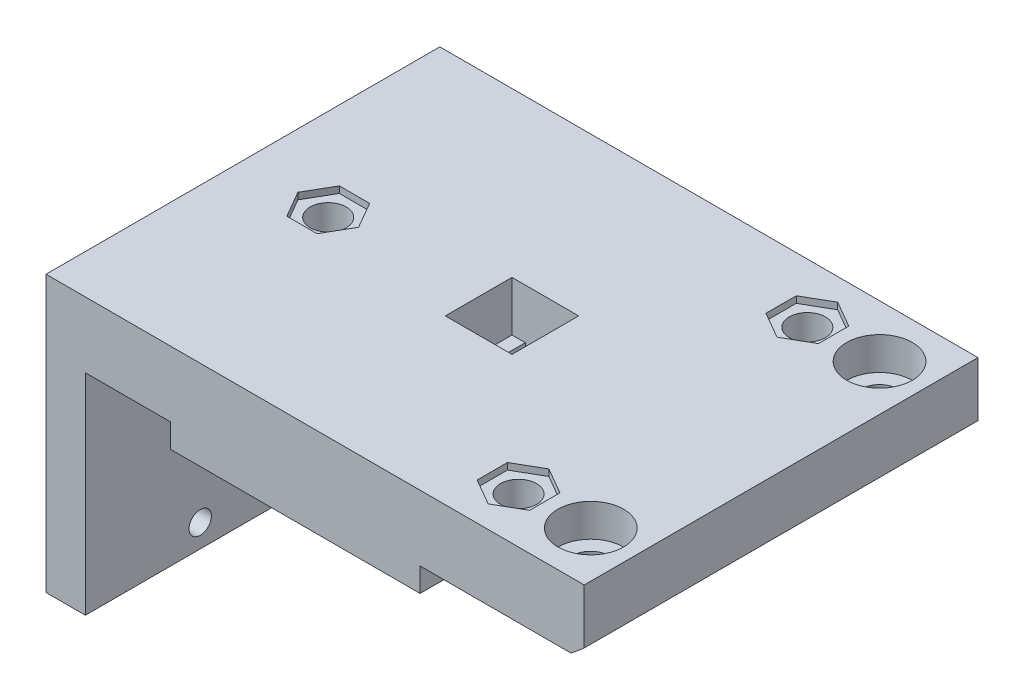
SolidWorks part; units mm, degrees
ref_plane "Front Plane" through (0, 0, 0) normal (0, 0, 1) x (1, 0, 0)
ref_plane "Top Plane" through (0, 0, 0) normal (0, 1, 0) x (1, 0, 0)
ref_plane "Right Plane" through (0, 0, 0) normal (1, 0, 0) x (0, 0, -1)
sketch "Sketch1" plane through (0, 0, 0) normal (0, 1, 0) x (1, 0, 0)
  line L1 (0, 0) -> (82, 0)
  line L2 (0, 0) -> (0, 60)
  line L3 (0, 60) -> (82, 60)
  line L4 (82, 0) -> (82, 60)
  dimension "D1" = 82
  dimension "D2" = 60
extrude "Boss-Extrude1" add sketch "Sketch1" along normal blind 10
sketch "Sketch2" plane through (0, 0, 0) normal (0, -1, 0) x (1, 0, 0)
  line L0 (0, 0) -> (82, 0) construction
  line L1 (0, -60) -> (6, -60)
  line L2 (0, -60) -> (0, 0)
  line L3 (0, 0) -> (6, 0)
  line L4 (6, -60) -> (6, 0)
  dimension "D1" = 6
extrude "Boss-Extrude2" add sketch "Sketch2" along normal blind 32
sketch "Sketch3" plane through (0, 0, 0) normal (-1, 0, 0) x (0, 0, 1)
  line L0 (0, -16) -> (-60, -16) construction
  line L1 (0, 10) -> (0, -32) construction
  line L2 (-60, 10) -> (-60, -32) construction
  line L5 (-60, -32) -> (-60, 0) construction
  line L6 (-17.5, -3.5) -> (-42.5, -3.5)
  line L7 (-17.5, -3.5) -> (-17.5, -28.5)
  line L8 (-17.5, -28.5) -> (-42.5, -28.5)
  line L9 (-42.5, -3.5) -> (-42.5, -28.5)
  line L10 (-17.5, -3.5) -> (-42.5, -28.5) construction
  line L11 (-17.5, -28.5) -> (-42.5, -3.5) construction
  point P7 (-30, -16)
  point P10 (0, 0)
  dimension "D1" = 25
hole_wizard "M3 Clearance Hole1" positions "Sketch4" profile "Sketch5" hole size "M3" standard "ANSI Metric" end condition through all
sketch "Sketch4" plane through (0, 0, 0) normal (-1, 0, 0) x (0, 0, 1)
  point P0 (-42.5, -28.5)
  point P3 (-42.5, -3.5)
  point P6 (-17.5, -3.5)
  point P9 (-17.5, -28.5)
sketch "Sketch5" plane through (0, -28.5, -42.5) normal (0, 1, 0) x (0, 0, 1)
  line L0 (0, 0) -> (0, 82)
  line L1 (0, 82) -> (1.7, 82)
  line L2 (1.7, 82) -> (1.7, 0)
  line L5 (1.7, 0) -> (0, 0)
  line L11 (0, -6.35) -> (0, 107.95) construction
  dimension "Thru Hole Dia." = 3.4
  dimension "Thru Hole Depth" = 82
ref_plane "Plane1" through (0, -16, 0) normal (0, -1, 0) x (-1, 0, 0)
ref_plane "Plane2" through (0, -4, 0) normal (0, -1, 0) x (-1, 0, 0)
ref_plane "Belt Plane" through (0, -3.624, 0) normal (0, -1, 0) x (-1, 0, 0)
sketch "Sketch7" plane through (0, 0, 0) normal (0, -1, 0) x (1, 0, 0)
  line L0 (82, -60) -> (6, -60) construction
  line L1 (19, -60) -> (57, -60)
  line L2 (19, -60) -> (19, 0)
  line L3 (19, 0) -> (57, 0)
  line L4 (57, -60) -> (57, 0)
  line L5 (6, 0) -> (82, 0) construction
  line L6 (6, -60) -> (6, 0) construction
  line L8 (82, 0) -> (82, -60) construction
  dimension "D1" = 13
  dimension "D2" = 25
extrude "Boss-Extrude3" add sketch "Sketch7" along normal up to surface (3.624 mm away) up to plane "Belt Plane"
sketch "Sketch8" plane through (0, -3.624, 0) normal (0, -1, 0) x (1, 0, 0)
  line L0 (41, -60) -> (41, 0) construction
  line L1 (19, -60) -> (57, -60) construction
  line L2 (57, 0) -> (19, 0) construction
  line L4 (6, -60) -> (6, 0) construction
  point P4 (0, 0)
  dimension "D1" = 35
hole_wizard "M4 Clearance Hole1" positions "Sketch9" profile "Sketch10" hole size "M4" standard "ANSI Metric" end condition through all
sketch "Sketch9" plane through (0, -3.624, 0) normal (0, -1, 0) x (-1, 0, 0)
  line L0 (-41, 60) -> (-41, 0) construction
  point P0 (-41, 30)
  point P5 (0, 0)
sketch "Sketch10" plane through (41, -3.624, -30) normal (1, 0, 0) x (0, 0, -1)
  line L0 (0, 0) -> (0, 13.624)
  line L1 (0, 13.624) -> (2.25, 13.624)
  line L2 (2.25, 13.624) -> (2.25, 0)
  line L5 (2.25, 0) -> (0, 0)
  line L11 (0, -6.35) -> (0, 107.95) construction
  dimension "Thru Hole Dia." = 4.5
  dimension "Thru Hole Depth" = 13.624
sketch "Sketch11" plane through (0, 10, 0) normal (0, 1, 0) x (1, 0, 0)
  line L1 (35.92, 24.92) -> (46.08, 24.92)
  line L2 (35.92, 24.92) -> (35.92, 35.08)
  line L3 (35.92, 35.08) -> (46.08, 35.08)
  line L4 (46.08, 24.92) -> (46.08, 35.08)
  line L5 (35.92, 24.92) -> (46.08, 35.08) construction
  line L6 (35.92, 35.08) -> (46.08, 24.92) construction
  point P0 (41, 30)
  dimension "D1" = 10.16
extrude "Cut-Extrude1" cut sketch "Sketch11" against normal offset from surface (9.124 mm away) 4.5 up to face at (41, -3.624, -32.25)
sketch "Sketch12" plane through (0, 0.876, 0) normal (0, 1, 0) x (1, 0, 0)
  line L0 (46.08, 35.08) -> (35.92, 35.08) construction
  line L1 (35.92, 24.92) -> (37.952, 24.92)
  line L2 (35.92, 24.92) -> (35.92, 35.08)
  line L3 (35.92, 35.08) -> (37.952, 35.08)
  line L4 (37.952, 24.92) -> (37.952, 35.08)
  line L6 (46.08, 24.92) -> (44.048, 24.92)
  line L7 (46.08, 24.92) -> (46.08, 35.08)
  line L8 (46.08, 35.08) -> (44.048, 35.08)
  line L9 (44.048, 24.92) -> (44.048, 35.08)
  dimension "D1" = 6.096
extrude "Boss-Extrude4" add sketch "Sketch12" along normal blind 1.524
ref_plane "Plane4" through (41, 0, 0) normal (-1, 0, 0) x (0, 0, 1)
sketch "Sketch15" plane through (0, 10, 0) normal (0, 1, 0) x (1, 0, 0)
  line L0 (75, 60) -> (75, 0) construction
  line L1 (82, 60) -> (0, 60) construction
  line L2 (0, 0) -> (82, 0) construction
  line L3 (82, 0) -> (82, 60) construction
  point P8 (75, 52)
  point P9 (75, 8)
  dimension "D1" = 7
  dimension "D2" = 8
  dimension "D3" = 8
hole_wizard "CBORE for M5 SHCS2" positions "Sketch18" profile "Sketch19" counterbore size "M5" standard "ANSI Metric" end condition through all
sketch "Sketch18" plane through (0, 10, 0) normal (0, 1, 0) x (1, 0, 0)
  point P0 (75, 52)
  point P3 (75, 8)
sketch "Sketch19" plane through (75, 10, -52) normal (1, 0, 0) x (0, 0, 1)
  line L0 (0, 0) -> (0, 42)
  line L1 (0, 42) -> (2.75, 42)
  line L3 (2.75, 42) -> (2.75, 5)
  line L4 (2.75, 5) -> (5, 5)
  line L5 (5, 5) -> (5, 0)
  line L7 (5, 0) -> (0, 0)
  line L11 (0, -6.35) -> (0, 107.95) construction
  dimension "Thru Hole Dia." = 5.5
  dimension "Thru Hole Depth" = 42
  dimension "C'Bore Dia." = 10
  dimension "C'Bore Depth" = 5
chamfer "Chamfer1" distance 2 angle 40 1 edges at (82, 0, -30) first distance on face at (75, 0, -54.75)
sketch "Sketch20" plane through (0, 10, 0) normal (0, 1, 0) x (1, 0, 0)
  line L0 (64, 0) -> (64, 60) construction
  line L1 (0, 0) -> (82, 0) construction
  line L2 (82, 60) -> (0, 60) construction
  line L3 (64, 60) -> (13, 30) construction
  line L5 (13, 30) -> (64, 0) construction
  line L6 (13, 30) -> (0, 30) construction
  line L7 (0, 60) -> (0, 0) construction
  line L8 (64, 12.6188) -> (60, 10.3094)
  line L9 (60, 10.3094) -> (60, 5.6906)
  line L10 (60, 5.6906) -> (64, 3.3812)
  line L11 (64, 3.3812) -> (68, 5.6906)
  line L12 (68, 5.6906) -> (68, 10.3094)
  line L13 (68, 10.3094) -> (64, 12.6188)
  line L14 (64, 47.3812) -> (68, 49.6906)
  line L15 (68, 49.6906) -> (68, 54.3094)
  line L16 (68, 54.3094) -> (64, 56.6188)
  line L17 (64, 56.6188) -> (60, 54.3094)
  line L18 (60, 54.3094) -> (60, 49.6906)
  line L19 (60, 49.6906) -> (64, 47.3812)
  line L20 (10.6906, 26) -> (15.3094, 26)
  line L21 (15.3094, 26) -> (17.6188, 30)
  line L22 (17.6188, 30) -> (15.3094, 34)
  line L23 (15.3094, 34) -> (10.6906, 34)
  line L24 (10.6906, 34) -> (8.3812, 30)
  line L25 (8.3812, 30) -> (10.6906, 26)
  line L26 (82, 0) -> (82, 60) construction
  circle A0 centre (64, 8) radius 4 construction
  circle A1 centre (64, 52) radius 4 construction
  circle A2 centre (13, 30) radius 4 construction
  point P19 (0, 0)
  point P34 (63.0236, 9.2858)
  point P35 (5.5023, 31.0507)
  point P36 (63.4402, 8)
  dimension "D1" = 13
  dimension "D2" = 8
  dimension "D3" = 8
  dimension "D4" = 8
  dimension "D5" = 18
extrude "Cut-Extrude2" cut sketch "Sketch20" against normal blind 1
sketch "Sketch21" plane through (0, 0, 0) normal (0, -1, 0) x (1, 0, 0)
  line L0 (68, -10.3094) -> (64, -12.6188) construction
  line L1 (64, -12.6188) -> (60, -10.3094) construction
  line L2 (60, -10.3094) -> (60, -5.6906) construction
  line L3 (60, -5.6906) -> (64, -3.3812) construction
  line L4 (64, -3.3812) -> (68, -5.6906) construction
  line L5 (68, -5.6906) -> (68, -10.3094) construction
  line L6 (60, -49.6906) -> (64, -47.3812) construction
  line L7 (64, -47.3812) -> (68, -49.6906) construction
  line L8 (68, -49.6906) -> (68, -54.3094) construction
  line L9 (68, -54.3094) -> (64, -56.6188) construction
  line L10 (64, -56.6188) -> (60, -54.3094) construction
  line L11 (60, -54.3094) -> (60, -49.6906) construction
  line L12 (68, -10.3094) -> (64, -12.6188)
  line L13 (64, -12.6188) -> (60, -10.3094)
  line L14 (60, -10.3094) -> (60, -5.6906)
  line L15 (60, -5.6906) -> (64, -3.3812)
  line L16 (64, -3.3812) -> (68, -5.6906)
  line L17 (68, -5.6906) -> (68, -10.3094)
  line L18 (60, -49.6906) -> (64, -47.3812)
  line L19 (64, -47.3812) -> (68, -49.6906)
  line L20 (68, -49.6906) -> (68, -54.3094)
  line L21 (68, -54.3094) -> (64, -56.6188)
  line L22 (64, -56.6188) -> (60, -54.3094)
  line L23 (60, -54.3094) -> (60, -49.6906)
  line L24 (64, -56.6188) -> (64, -47.3812)
  line L25 (64, -12.6188) -> (64, -3.3812)
  line L26 (10.6906, -34) -> (15.3094, -26)
  line L32 (10.6906, -26) -> (8.3812, -30)
  line L33 (15.3094, -26) -> (10.6906, -26)
  line L34 (17.6188, -30) -> (15.3094, -26)
  line L35 (15.3094, -34) -> (17.6188, -30)
  line L36 (10.6906, -34) -> (15.3094, -34)
  line L37 (8.3812, -30) -> (10.6906, -34)
  line L38 (10.6906, -26) -> (8.3812, -30)
  line L39 (15.3094, -26) -> (10.6906, -26)
  line L40 (17.6188, -30) -> (15.3094, -26)
  line L41 (15.3094, -34) -> (17.6188, -30)
  line L42 (10.6906, -34) -> (15.3094, -34)
  line L43 (8.3812, -30) -> (10.6906, -34)
  dimension "D1" = 0
hole_wizard "CBORE for M5 SHCS3" positions "Sketch22" profile "Sketch23" counterbore size "M5" standard "ANSI Metric" end condition through all
sketch "Sketch22" plane through (0, 0, 0) normal (0, -1, 0) x (-1, 0, 0)
  line L0 (-64, 12.6188) -> (-64, 3.3812) construction
  line L1 (-64, 56.6188) -> (-64, 47.3812) construction
  line L2 (-10.6906, 34) -> (-15.3094, 26) construction
  point P0 (-64, 52)
  point P2 (-64, 8)
  point P11 (-13, 30)
  point P16 (0, 0)
sketch "Sketch23" plane through (64, 0, -52) normal (1, 0, 0) x (0, 0, -1)
  line L0 (0, 0) -> (0, 10)
  line L1 (0, 10) -> (2.75, 10)
  line L3 (2.75, 10) -> (2.75, 5)
  line L4 (2.75, 5) -> (5, 5)
  line L5 (5, 5) -> (5, 0)
  line L7 (5, 0) -> (0, 0)
  line L11 (0, -6.35) -> (0, 107.95) construction
  dimension "Thru Hole Dia." = 5.5
  dimension "Thru Hole Depth" = 10
  dimension "C'Bore Dia." = 10
  dimension "C'Bore Depth" = 5
